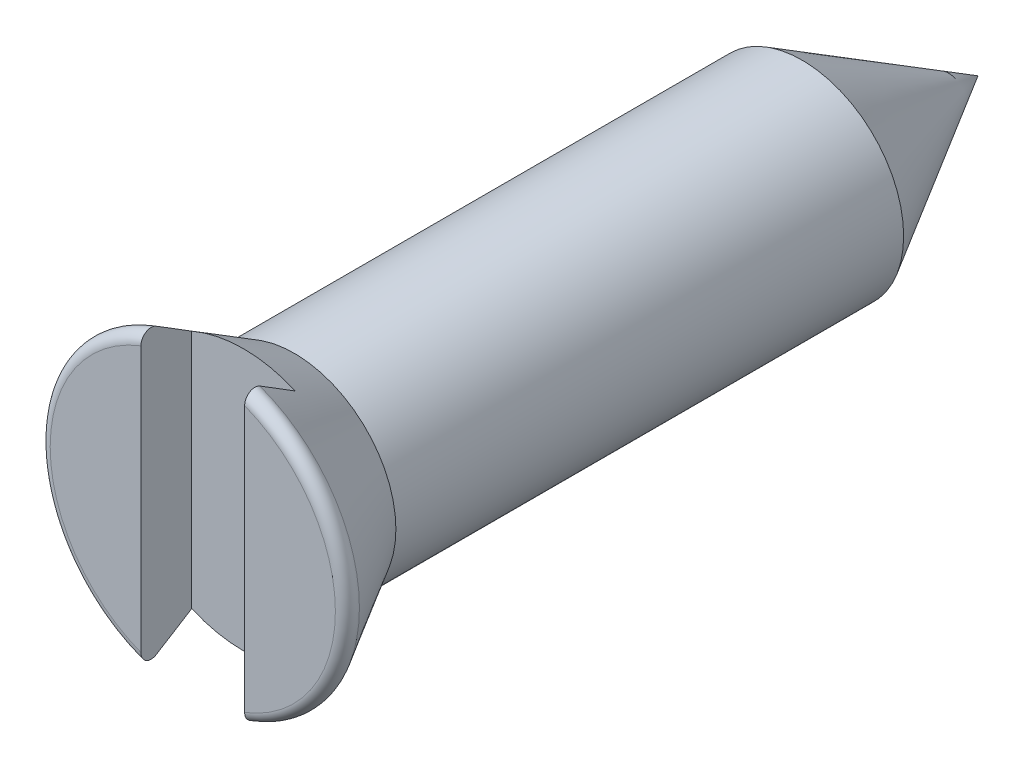
SolidWorks part; units mm, degrees
ref_plane "Front Plane" through (0, 0, 0) normal (0, 0, 1) x (1, 0, 0)
ref_plane "Top Plane" through (0, 0, 0) normal (0, 1, 0) x (1, 0, 0)
ref_plane "Right Plane" through (0, 0, 0) normal (1, 0, 0) x (0, 0, -1)
sketch "Sketch1" plane through (0, 0, 0) normal (0, 0, 1) x (1, 0, 0)
  circle A0 centre (0, 0) radius 1
  dimension "D1" = 2
extrude "Boss-Extrude1" add sketch "Sketch1" along normal blind 5
extrude "Boss-Extrude2" add sketch "Sketch1<3>" against normal blind 12 draft 30
sketch "Sketch1<3>" plane through (0, 0, 0) normal (0, 0, 1) x (1, 0, 0) same geometry as "Sketch1"
sketch "Sketch2" plane through (0, 0, 5) normal (0, 0, 1) x (1, 0, 0)
  circle A0 centre (0, 0) radius 1
extrude "Boss-Extrude3" add sketch "Sketch2" along normal blind 1 draft 30 draft outward yes
sketch "Sketch3" plane through (0, 0, 6) normal (0, 0, 1) x (1, 0, 0)
  line L0 (-0.5106, 1.4924) -> (-0.5106, -1.4924)
  line L2 (0.5106, -1.4924) -> (0.5106, 1.4924)
  circle A0 centre (0, 0) radius 1.5774 construction
  arc A1 (-0.5106, -1.4924) -> (0.5106, -1.4924) centre (0, 0) ccw
  arc A2 (-0.5106, 1.4924) -> (0.5106, 1.4924) centre (0, 0) cw
extrude "Cut-Extrude1" cut sketch "Sketch3" against normal blind 0.5
ref_plane "Plane1" through (0, 0, 5) normal (0, 0, 1) x (1, 0, 0)
fillet "Fillet2" radius 0.1 2 edges at (-1.5774, 0, 6) (1.5774, 0, 6)
